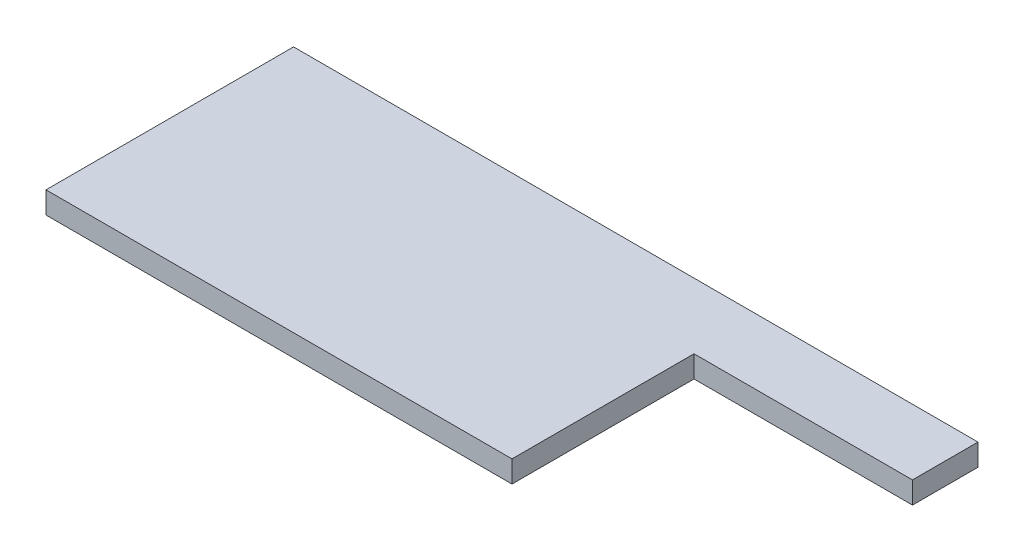
SolidWorks part; units mm, degrees
material "Pine"
ref_plane "Front Plane" through (0, 0, 0) normal (0, 0, 1) x (1, 0, 0)
ref_plane "Top Plane" through (0, 0, 0) normal (0, 1, 0) x (1, 0, 0)
ref_plane "Right Plane" through (0, 0, 0) normal (1, 0, 0) x (0, 0, -1)
sketch "Sketch1" plane through (0, 0, 0) normal (0, 1, 0) x (1, 0, 0)
  line L1 (0, 0) -> (188, 0)
  line L2 (0, 0) -> (0, 68)
  line L3 (0, 68) -> (188, 68)
  line L4 (188, 0) -> (188, 68)
  dimension "D1" = 188
  dimension "D2" = 68
extrude "Boss-Extrude1" add sketch "Sketch1" along normal blind 6
sketch "Sketch2" plane through (0, 6, 0) normal (0, 1, 0) x (1, 0, 0)
  line L0 (188, 0) -> (188, 68) construction
  line L1 (188, 50) -> (128, 50)
  line L2 (188, 50) -> (188, 0)
  line L3 (188, 0) -> (128, 0)
  line L4 (128, 50) -> (128, 0)
  line L5 (0, 0) -> (188, 0) construction
  dimension "D1" = 50
  dimension "D2" = 60
extrude "Cut-Extrude1" cut sketch "Sketch2" against normal through all
equation "\"BoardThickness\"= 6"
equation "\"D1@Sketch1\"=200-\"BoardThickness\"*2"
equation "\"D2@Sketch1\"=100-20-\"BoardThickness\"*2"
equation "\"D1@Boss-Extrude1\"=\"BoardThickness\""
